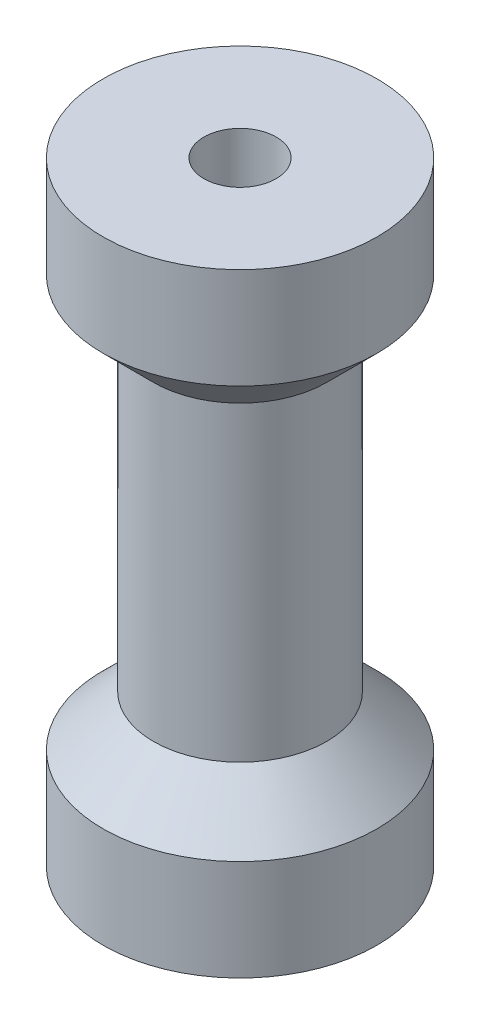
SolidWorks part; units mm, degrees
material "PA Type 6"
ref_plane "Front Plane" through (0, 0, 0) normal (0, 0, 1) x (1, 0, 0)
ref_plane "Top Plane" through (0, 0, 0) normal (0, 1, 0) x (1, 0, 0)
ref_plane "Right Plane" through (0, 0, 0) normal (1, 0, 0) x (0, 0, -1)
sketch "Sketch1" plane through (0, 0, 0) normal (0, 0, 1) x (1, 0, 0)
  line L0 (2.15, 0) -> (2.15, 36.5)
  line L1 (2.15, 36.5) -> (8.15, 36.5)
  line L2 (5.15, 30.5) -> (5.15, 6)
  line L3 (8.15, 0) -> (2.15, 0)
  line L4 (0, -42.8219) -> (0, 42.8219) construction
  line L5 (8.15, 36.5) -> (8.15, 30.5)
  line L6 (8.15, 30.5) -> (5.15, 30.5)
  line L7 (8.15, 0) -> (8.15, 6)
  line L8 (8.15, 6) -> (5.15, 6)
  point P8 (0, 0)
  dimension "D1" = 36.5
  dimension "D2" = 6
  dimension "D3" = 2.15
  dimension "D4" = 6
  dimension "D5" = 3
revolve "Revolve1" add sketch "Sketch1" angle 360 about L4
chamfer "Chamfer1" distance 3 angle 45 2 edges at (5.15, 6, 0) (5.15, 30.5, 0)
